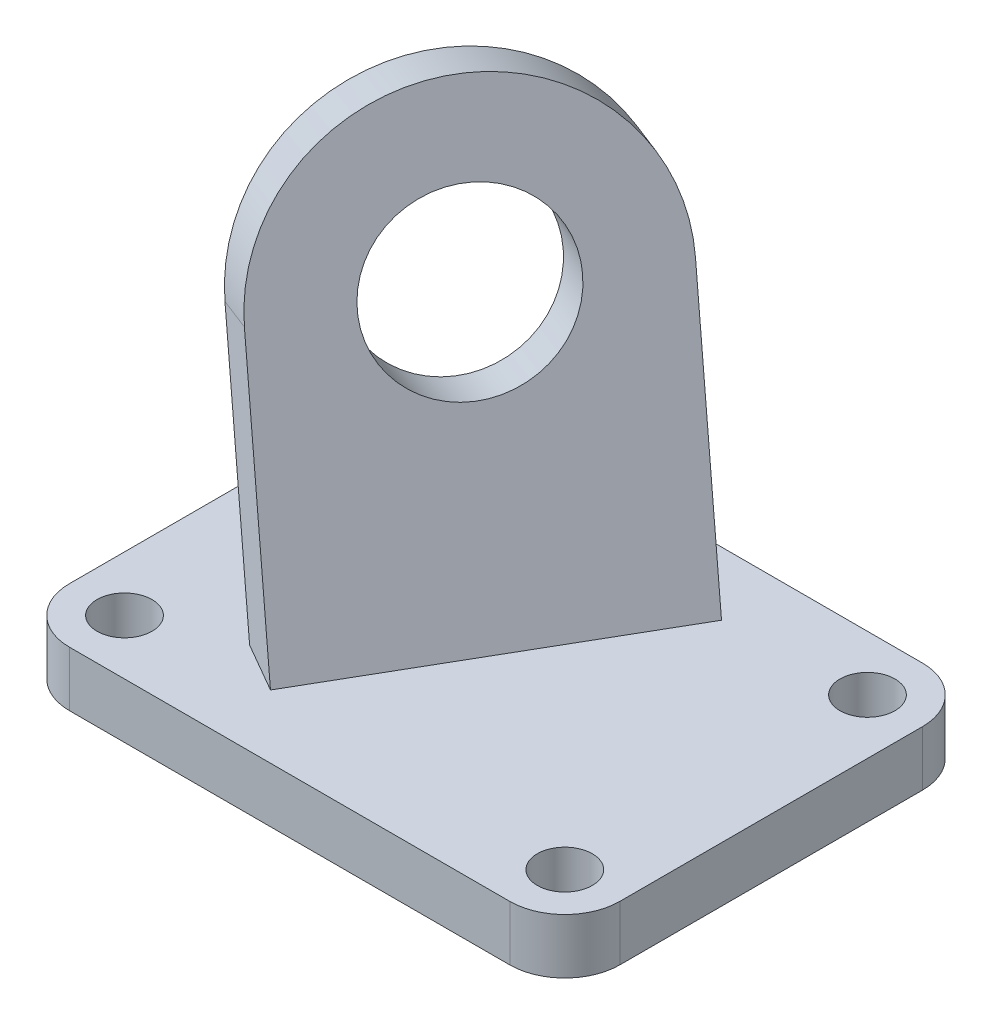
SolidWorks part; units mm, degrees
ref_plane "前基準面" through (0, 0, 0) normal (0, 0, 1) x (1, 0, 0)
ref_plane "上基準面" through (0, 0, 0) normal (0, 1, 0) x (1, 0, 0)
ref_plane "右基準面" through (0, 0, 0) normal (1, 0, 0) x (0, 0, -1)
sketch "草圖1" plane through (0, 0, 0) normal (0, 1, 0) x (1, 0, 0)
  line L1 (-40, -37.5) -> (40, -37.5)
  line L2 (-50, -27.5) -> (-50, 27.5)
  line L3 (-40, 37.5) -> (40, 37.5)
  line L4 (50, -27.5) -> (50, 27.5)
  line L5 (-50, -37.5) -> (50, 37.5) construction
  line L6 (-50, 37.5) -> (50, -37.5) construction
  arc A0 (-50, 27.5) -> (-40, 37.5) centre (-40, 27.5) cw
  arc A1 (-40, -37.5) -> (-50, -27.5) centre (-40, -27.5) cw
  arc A2 (50, -27.5) -> (40, -37.5) centre (40, -27.5) cw
  arc A3 (50, 27.5) -> (40, 37.5) centre (40, 27.5) ccw
  circle A4 centre (-40, 27.5) radius 5
  circle A5 centre (40, 27.5) radius 5
  circle A6 centre (-40, -27.5) radius 5
  circle A7 centre (40, -27.5) radius 5
  point P0 (0, 0)
  dimension "D3" = 10
  dimension "D4" = 10
  dimension "D5" = 10
  dimension "D6" = 10
  dimension "D7" = 10
  dimension "D1" = 75
  dimension "D2" = 100
extrude "填料-伸長1" add sketch "草圖1" against normal blind 10
ref_axis "基準軸1" through (0, 32.0922, 0) along (0, -1, 0)
ref_plane "平面1" through (0, 0, 0) normal (0.866, 0, 0.5) x (0, -1, 0)
ref_axis "基準軸2" through (-23.8157, 0, 41.25) along (0.5, 0, -0.866)
ref_plane "平面2" through (0, 0, 0) normal (0.8365, 0.2588, 0.483) x (0.5, 0, -0.866)
sketch "草圖3" plane through (0, 0, 0) normal (0.8365, 0.2588, 0.483) x (0.5, 0, -0.866)
  line L6 (-30, 50) -> (-30, 0)
  line L7 (-30, 0) -> (30, 0)
  line L8 (30, 0) -> (30, 50)
  circle A0 centre (0, 50) radius 15
  arc A1 (-30, 50) -> (30, 50) centre (0, 50) cw
  point P14 (0, 0)
  dimension "D1" = 30
  dimension "D2" = 30
  dimension "D3" = 50
extrude "填料-伸長2" add sketch "草圖3" against normal blind 10
